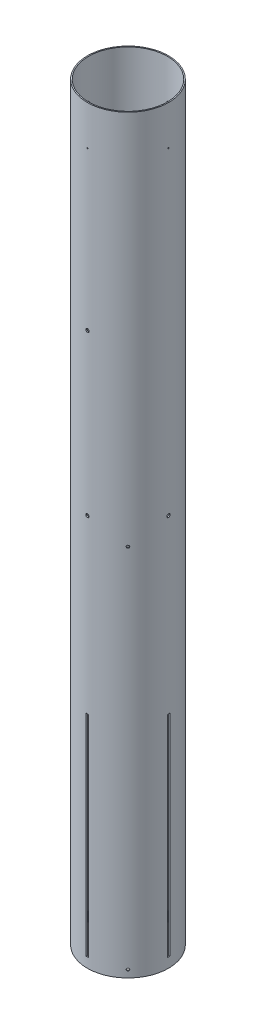
SolidWorks part; units mm, degrees
material "E-Glass Fiber"
ref_plane "Front Plane" through (0, 0, 0) normal (0, 0, 1) x (1, 0, 0)
ref_plane "Top Plane" through (0, 0, 0) normal (0, 1, 0) x (1, 0, 0)
ref_plane "Right Plane" through (0, 0, 0) normal (1, 0, 0) x (0, 0, -1)
sketch "Sustainer Tube Profile" plane through (0, 0, 0) normal (0, 1, 0) x (1, 0, 0)
  circle A0 centre (0, 0) radius 76.2
  circle A1 centre (0, 0) radius 78.359
  dimension "D2" = 156.718
extrude "Sustainer Tube Body" add sketch "Sustainer Tube Profile" along normal blind 1447.8
ref_plane "Plane1" through (0, 0, 78.359) normal (0, 0, 1) x (1, 0, 0)
sketch "Fin Slot Profile" plane through (0, 0, 78.359) normal (0, 0, 1) x (1, 0, 0)
  line L0 (0, 0) -> (0, 1447.8) construction
  line L5 (76.2, 1447.8) -> (-76.2, 1447.8) construction
  line L6 (-78.359, 0) -> (78.359, 0) construction
  line L7 (2.3813, 19.05) -> (-2.3813, 19.05)
  line L8 (0, 19.05) -> (0, 425.45)
  line L9 (2.3813, 425.45) -> (-2.3813, 425.45)
  line L10 (-2.3813, 19.05) -> (-2.3813, 425.45)
  line L11 (2.3813, 19.05) -> (2.3813, 425.45)
  dimension "D1" = 406.4
  dimension "D2" = 19.05
  dimension "D3" = 2.3813
extrude "Fin Slot Cut" cut sketch "Fin Slot Profile" against normal up to surface (2.1962 mm away) contours L7 L11 L9 L8 | L10 L7 L8 L9 region at (1.1906, 222.25, 78.359) region at (-1.1906, 222.25, 78.359) up to face at (0, 1447.8, 76.2)
pattern_circular "Fin Slot Pattern" count 4 over 360 about axis through (0, 1447.8, 0) along (0, 1, 0) of "Fin Slot Cut"
sketch "Sketch1" plane through (0, 0, 0) normal (0, 0, 1) x (1, 0, 0)
  line L0 (76.2, 1447.8) -> (-76.2, 1447.8) construction
  circle A0 centre (0, 1371.6) radius 1.143
  dimension "D1" = 2.286
  dimension "D2" = 76.2
extrude "Cut-Extrude1" cut sketch "Sketch1" against normal through all both and the other way through all
pattern_circular "CirPattern1" count 4 over 360 about axis through (0, 1447.8, 0) along (0, 1, 0) of "Cut-Extrude1"
sketch "Sketch2" plane through (0, 0, 0) normal (0, 0, 1) x (1, 0, 0)
  line L0 (76.2, 1447.8) -> (-76.2, 1447.8) construction
  circle A0 centre (0, 1066.8) radius 3.175
  dimension "D1" = 6.35
  dimension "D2" = 381
extrude "Cut-Extrude2" cut sketch "Sketch2" against normal through all both and the other way through all
sketch "Sketch3" plane through (0, 0, 0) normal (0, 0, 1) x (1, 0, 0)
  line L0 (78.359, 1447.8) -> (-78.359, 1447.8) construction
  circle A0 centre (0, 756.9962) radius 3.175
  dimension "D2" = 6.35
  dimension "D1" = 690.8038
extrude "Cut-Extrude3" cut sketch "Sketch3" against normal through all both and the other way through all
pattern_circular "CirPattern2" count 4 over 360 about axis through (0, 1447.8, 0) along (0, 1, 0) of "Cut-Extrude3"
ref_plane "Plane2" through (55.4082, 0, 55.4082) normal (0.7071, 0, 0.7071) x (0, -1, 0)
sketch "Sketch4" plane through (55.4082, 0, 55.4082) normal (0.7071, 0, 0.7071) x (0, -1, 0)
  circle A0 centre (-14.0462, 0) radius 2.5019
  circle A1 centre (-721.2584, 0) radius 2.5019
  dimension "D2" = 14.0462
  dimension "D3" = 721.2584
extrude "Cut-Extrude4" cut sketch "Sketch4" against normal up to surface and the other way through all up to face at (-76.1373, 756.269, 3.0906)
equation "\"Length\" = 57"
equation "\"Outer Diameter\"= 6.17"
equation "\"Inner Diameter\"= 6"
equation "\"Wall Thickness\"= 0.085"
equation "\"D1@Sustainer Tube Profile\" = \"Inner Diameter\""
equation "\"D2@Sustainer Tube Profile\" = \"Outer Diameter\""
equation "\"D1@Sustainer Tube Body\" = \"Length\""
equation "\"Root Chord\"= 16"
equation "\"Fin Offset\"= 3 / 4"
equation "\"D1@Fin Slot Profile\"=\"Root Chord\" "
equation "\"D2@Fin Slot Profile\" = \"Fin Offset\""
equation "\"Fin Thickness\"= ( 3 / 16 ) / 2"
equation "\"D3@Fin Slot Profile\"=\"Fin Thickness\""
equation "\"Shear Pin Dia\"= 3 / 32"
equation "\"Shear Pin Offset\"= 3"
equation "\"Bulkhead Screw Dia\"= 1 / 4"
equation "\"Bulkhead Screw Offset\" = 24.197 + 3"
equation "\"Rail Button Dia\"= 0.197"
equation "\"Rail Button Aft Offset\"= 0.553"
equation "\"Rail Button Forward Offset\"= 28.396"
equation "\"Vent Hole Dia\"= 1 / 4"
equation "\"Vent Hole Offset\"= 15"
equation "\"D1@Sketch2\"=\"Vent Hole Dia\""
equation "\"D2@Sketch2\"=\"Vent Hole Offset\""
equation "\"D1@Sketch3\"=\"Bulkhead Screw Offset\""
equation "\"D2@Sketch3\"=\"Bulkhead Screw Dia\""
equation "\"D1@Sketch4\"=\"Rail Button Dia\""
equation "\"D2@Sketch4\"=\"Rail Button Aft Offset\""
equation "\"D3@Sketch4\"=\"Rail Button Forward Offset\""
